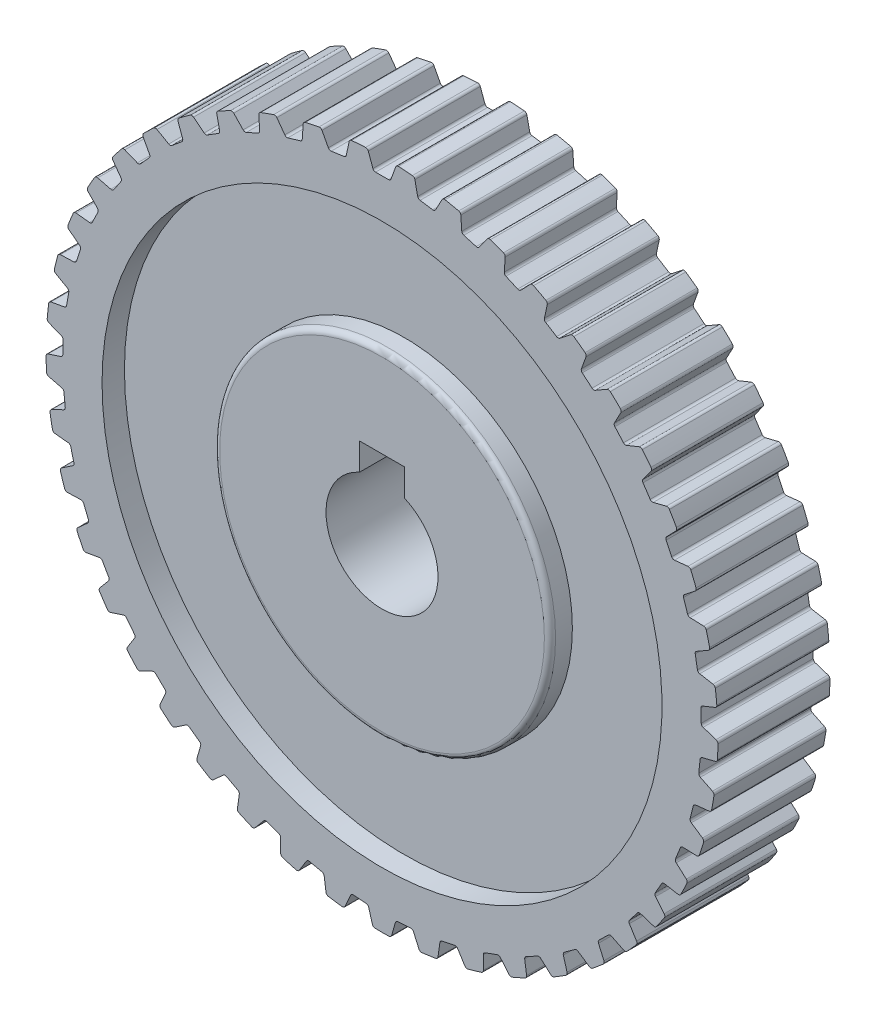
SolidWorks part; units mm, degrees
ref_plane "Front Plane" through (0, 0, 0) normal (0, 0, 1) x (1, 0, 0)
ref_plane "Top Plane" through (0, 0, 0) normal (0, 1, 0) x (1, 0, 0)
ref_plane "Right Plane" through (0, 0, 0) normal (1, 0, 0) x (0, 0, -1)
sketch "Sketch1" plane through (0, 0, 0) normal (0, 0, 1) x (1, 0, 0)
  line L1 (-2, 7) -> (2, 7)
  line L2 (-2, 7) -> (-2, 4.5826)
  line L4 (2, 7) -> (2, 4.5826)
  circle A0 centre (0, 0) radius 30
  arc A1 (-2, 4.5826) -> (2, 4.5826) centre (0, 0) ccw
  point P4 (0, 5)
  dimension "D1" = 60
  dimension "D2" = 10
  dimension "D3" = 4
  dimension "D4" = 7
  dimension "D5" = 2.4174
extrude "Boss-Extrude1" add sketch "Sketch1" along normal mid plane 10
sketch "Sketch2" plane through (0, 0, 5) normal (0, 0, 1) x (1, 0, 0)
  line L0 (0, 0) -> (0, 30) construction
  line L1 (-0.75, 28.5) -> (0.75, 28.5)
  line L2 (0.75, 28.5) -> (1.2859, 29.9724)
  line L3 (-0.75, 28.5) -> (-1.2859, 29.9724)
  circle A0 centre (0, 0) radius 30 construction
  arc A1 (-1.2859, 29.9724) -> (1.2859, 29.9724) centre (0, 29.2002) cw
  point P10 (0, 28.5)
  dimension "D3" = 1.5
  dimension "D1" = 0.75
  dimension "D2" = 20
  dimension "D4" = 28.5
extrude "Cut-Extrude3" cut sketch "Sketch2" against normal through all
pattern_circular "CirPattern2" count 45 over 360 about axis through (0, 0, 5) along (0, 0, 1) of "Cut-Extrude3"
sketch "Sketch3" plane through (0, 0, -5) normal (0, 0, -1) x (-1, 0, 0)
  circle A0 centre (0, 0) radius 15
  circle A1 centre (0, 0) radius 25
  dimension "D1" = 30
  dimension "D2" = 50
extrude "Cut-Extrude4" cut sketch "Sketch3" against normal blind 2
mirror "Mirror1" about plane through (0, 0, 0) normal (0, 0, 1) of "Cut-Extrude4"
fillet "Fillet1" radius 0.5 2 edges at (-15, 0, -5) (-15, 0, 5)
fillet "Fillet2" radius 0.25 180 edges at (28.4223, -2.2332, 0) (29.9427, -1.8541, 0) (29.999, -0.2391, 0) (28.5088, 0.2451, 0) (28.4565, 1.7442, 0) (29.9093, 2.3312, 0) (29.7404, 3.9383, 0) (28.1973, 4.2104, 0) (27.9368, 5.6876, 0) (29.2938, 6.471, 0) (28.9028, 8.039, 0) (27.3369, 8.0937, 0) (26.8733, 9.5203, 0) (28.1081, 10.485, 0) (27.5027, 11.9833, 0) (25.9444, 11.8195, 0) (25.2869, 13.1677, 0) (25.5673, 15.6943, 0) (24.047, 15.3152, 0) (23.2082, 16.5588, 0) (24.1292, 17.8264, 0) (23.1343, 19.0998, 0) (21.6815, 18.5129, 0) (20.6778, 19.6276, 0) (21.4134, 21.0111, 0) (20.251, 22.1336, 0) (18.894, 21.3502, 0) (17.7449, 22.3144, 0) (18.2808, 23.7868, 0) (16.9735, 24.7366, 0) (15.7387, 23.7719, 0) (14.4667, 24.5668, 0) (14.7924, 26.0995, 0) (13.3656, 26.8581, 0) (12.2772, 25.731, 0) (10.9068, 26.3411, 0) (11.0161, 27.9042, 0) (9.4976, 28.4569, 0) (8.5766, 27.1892, 0) (7.1347, 27.6027, 0) (7.0254, 29.1658, 0) (5.4448, 29.5018, 0) (4.7091, 28.1183, 0) (3.2237, 28.327, 0) (2.898, 29.8597, 0) (1.2859, 29.9724, 0) (0.75, 28.5, 0) (-0.75, 28.5, 0) (-1.2859, 29.9724, 0) (-2.898, 29.8597, 0) (-3.2237, 28.327, 0) (-4.7091, 28.1183, 0) (-5.4448, 29.5018, 0) (-7.0254, 29.1658, 0) (-7.1347, 27.6027, 0) (-8.5766, 27.1892, 0) (-9.4976, 28.4569, 0) (-11.0161, 27.9042, 0) (-10.9068, 26.3411, 0) (-12.2772, 25.731, 0) (-13.3656, 26.8581, 0) (-14.7924, 26.0995, 0) (-14.4667, 24.5668, 0) (-15.7387, 23.7719, 0) (-16.9735, 24.7366, 0) (-18.2808, 23.7868, 0) (-17.7449, 22.3144, 0) (-18.894, 21.3502, 0) (-20.251, 22.1336, 0) (-21.4134, 21.0111, 0) (-20.6778, 19.6276, 0) (-21.6815, 18.5129, 0) (-23.1343, 19.0998, 0) (-24.1292, 17.8264, 0) (-23.2082, 16.5588, 0) (-24.047, 15.3152, 0) (-25.5673, 15.6943, 0) (-26.3753, 14.2948, 0) (-25.2869, 13.1677, 0) (-25.9444, 11.8195, 0) (-27.5027, 11.9833, 0) (-28.1081, 10.485, 0) (-26.8733, 9.5203, 0) (-27.3369, 8.0937, 0) (-28.9028, 8.039, 0) (-29.2938, 6.471, 0) (-27.9368, 5.6876, 0) (-28.1973, 4.2104, 0) (-29.7404, 3.9383, 0) (-29.9093, 2.3312, 0) (-28.4565, 1.7442, 0) (-28.5088, 0.2451, 0) (-29.999, -0.2391, 0) (-29.9427, -1.8541, 0) (-28.4223, -2.2332, 0) (-28.2655, -3.725, 0) (-29.6738, -4.4118, 0) (-29.3932, -6.0033, 0) (-27.8349, -6.1671, 0) (-27.472, -7.6225, 0) (-28.771, -8.4987, 0) (-28.2717, -10.0356, 0) (-26.7057, -9.9809, 0) (-26.1438, -11.3717, 0) (-27.3082, -12.4202, 0) (-26.5998, -13.8726, 0) (-25.0567, -13.6005, 0) (-24.3067, -14.8995, 0) (-25.3139, -16.0999, 0) (-24.4103, -17.4396, 0) (-22.9201, -16.9553, 0) (-21.9966, -18.1374, 0) (-22.8269, -19.4662, 0) (-21.7456, -20.6671, 0) (-20.3373, -19.9802, 0) (-19.2583, -21.0222, 0) (-19.8956, -22.4536, 0) (-18.6577, -23.4924, 0) (-17.3586, -22.6161, 0) (-16.1451, -23.4978, 0) (-16.577, -25.004, 0) (-15.2066, -25.8604, 0) (-14.0422, -24.8119, 0) (-12.7177, -25.5161, 0) (-12.9358, -27.0678, 0) (-11.4595, -27.7251, 0) (-10.4523, -26.5247, 0) (-9.0428, -27.0378, 0) (-9.0428, -28.6047, 0) (-7.4894, -29.0501, 0) (-6.6591, -27.7213, 0) (-5.1919, -28.0331, 0) (-4.9738, -29.5848, 0) (-3.3736, -29.8097, 0) (-2.7362, -28.3783, 0) (-1.2399, -28.4829, 0) (-0.808, -29.9891, 0) (0.808, -29.9891, 0) (1.2399, -28.4829, 0) (2.7362, -28.3783, 0) (3.3736, -29.8097, 0) (4.9738, -29.5848, 0) (5.1919, -28.0331, 0) (6.6591, -27.7213, 0) (7.4894, -29.0501, 0) (9.0428, -28.6047, 0) (9.0428, -27.0378, 0) (10.4523, -26.5247, 0) (11.4595, -27.7251, 0) (12.9358, -27.0678, 0) (12.7177, -25.5161, 0) (14.0422, -24.8119, 0) (15.2066, -25.8604, 0) (16.577, -25.004, 0) (16.1451, -23.4978, 0) (17.3586, -22.6161, 0) (18.6577, -23.4924, 0) (19.8956, -22.4536, 0) (19.2583, -21.0222, 0) (20.3373, -19.9802, 0) (21.7456, -20.6671, 0) (22.8269, -19.4662, 0) (21.9966, -18.1374, 0) (22.9201, -16.9553, 0) (24.4103, -17.4396, 0) (25.3139, -16.0999, 0) (24.3067, -14.8995, 0) (25.0567, -13.6005, 0) (26.5998, -13.8726, 0) (27.3082, -12.4202, 0) (26.1438, -11.3717, 0) (26.7057, -9.9809, 0) (28.2717, -10.0356, 0) (28.771, -8.4987, 0) (27.472, -7.6225, 0) (27.8349, -6.1671, 0) (29.3932, -6.0033, 0) (29.6738, -4.4118, 0) (28.2655, -3.725, 0) (26.3753, 14.2948, 0)
